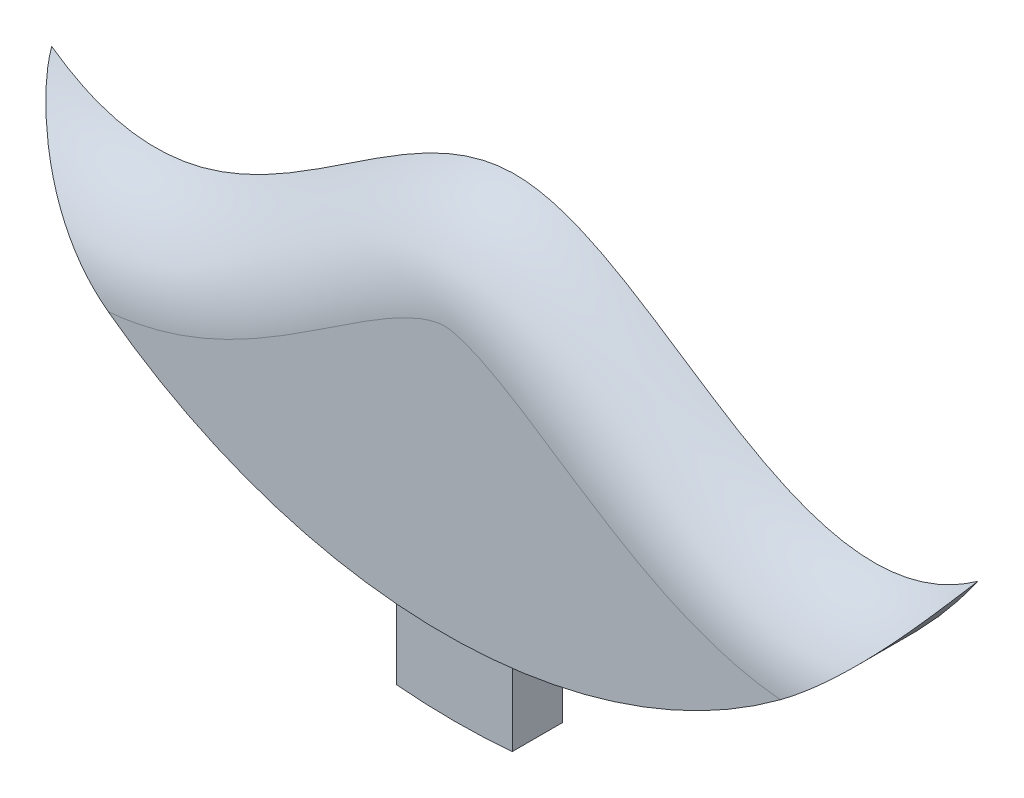
SolidWorks part; units mm, degrees
note: '?' marks a value the reader was unsure of.
ref_plane "Front" through (0, 0, 0) normal (0, 0, 1) x (1, 0, 0)
ref_plane "Top" through (0, 0, 0) normal (0, 1, 0) x (1, 0, 0)
ref_plane "Right" through (0, 0, 0) normal (1, 0, 0) x (0, 0, -1)
ref_axis "Center Axis" through (0, 0, -0.35) along (0, 0, 1)?
sketch "Sketch1" plane through (0, 0, 0) normal (0, 0, 1) x (1, 0, 0)
  circle A0 centre (0, 0) radius 56
  dimension "D1" = 112
extrude "Boss-Extrude1" add sketch "Sketch1" along normal blind 7
sketch "Sketch2" plane through (0, 0, 7) normal (0, 0, 1) x (1, 0, 0)
  line L1 (-69.4839, 80) -> (69.4839, 80)
  line L2 (-69.4839, 80) -> (-69.4839, -20)
  line L3 (-69.4839, -20) -> (69.4839, -20)
  line L4 (69.4839, 80) -> (69.4839, -20)
  dimension "D1" = 20
  dimension "D2" = 100
extrude "Cut-Extrude1" cut sketch "Sketch2" against normal blind 30
sketch "Sketch3" plane through (0, 0, 7) normal (0, 0, 1) x (1, 0, 0)
  line L0 (-52.3068, -20) -> (52.3068, -20) construction
  line L1 (-45.9565, -32) -> (-61.7818, -32)
  line L2 (-61.7818, -32) -> (-61.7818, -9.4853)
  line L3 (-61.7818, -9.4853) -> (56.9108, -9.4853)
  line L4 (56.9108, -9.4853) -> (56.9108, -32)
  line L5 (56.9108, -32) -> (45.9565, -32)
  arc A0 (-52.3068, -20) -> (52.3068, -20) centre (0, 0) ccw construction
  spline S0 degree 3 poles (-45.9565, -32) (-28.4222, -44.4975) (0, 4.4975) (28.4222, -44.4975) (45.9565, -32) knots 0 0 0 0 0.5 1 1 1 1
  dimension "D1" = 12
  dimension "D2" = 12
  dimension "D3" = 24
  dimension "D4" = 24
  dimension "D5" = 12
  dimension "D6" = 12
extrude "Cut-Extrude2" cut sketch "Sketch3" against normal blind 30
fillet "Fillet1" radius 10 1 edges
ref_plane "Plane1" through (0, -50, 0) normal (0, 1, 0) x (1, 0, 0)
sketch "Sketch4" plane through (0, -50, 0) normal (0, 1, 0) x (1, 0, 0)
  line L0 (45.9565, 0) -> (-45.9565, 0) construction
  line L1 (-5.75, -6) -> (5.75, -6)
  line L2 (-5.75, -6) -> (-5.75, -1)
  line L3 (-5.75, -1) -> (5.75, -1)
  line L4 (5.75, -6) -> (5.75, -1)
  line L5 (-5.75, -6) -> (5.75, -1) construction
  line L6 (-5.75, -1) -> (5.75, -6) construction
  point P0 (0, -3.5)
  dimension "D1" = 11.5
  dimension "D2" = 5
  dimension "D3" = 3.5
  dimension "D4" = 0
extrude "Boss-Extrude2" add sketch "Sketch4" against normal blind 20
sketch "Sketch5" plane through (0, 0, 7) normal (0, 0, 1) x (1, 0, 0)
  line L0 (-13.999, -62.4502) -> (-13.999, -75.0712)
  line L1 (-13.999, -75.0712) -> (14.564, -75.0712)
  line L2 (14.564, -75.0712) -> (15.5252, -62.0884)
  arc A1 (15.5252, -62.0884) -> (-13.999, -62.4502) centre (0, 0) cw
  dimension "D1" = 64
extrude "Cut-Extrude3" cut sketch "Sketch5" against normal blind 10
